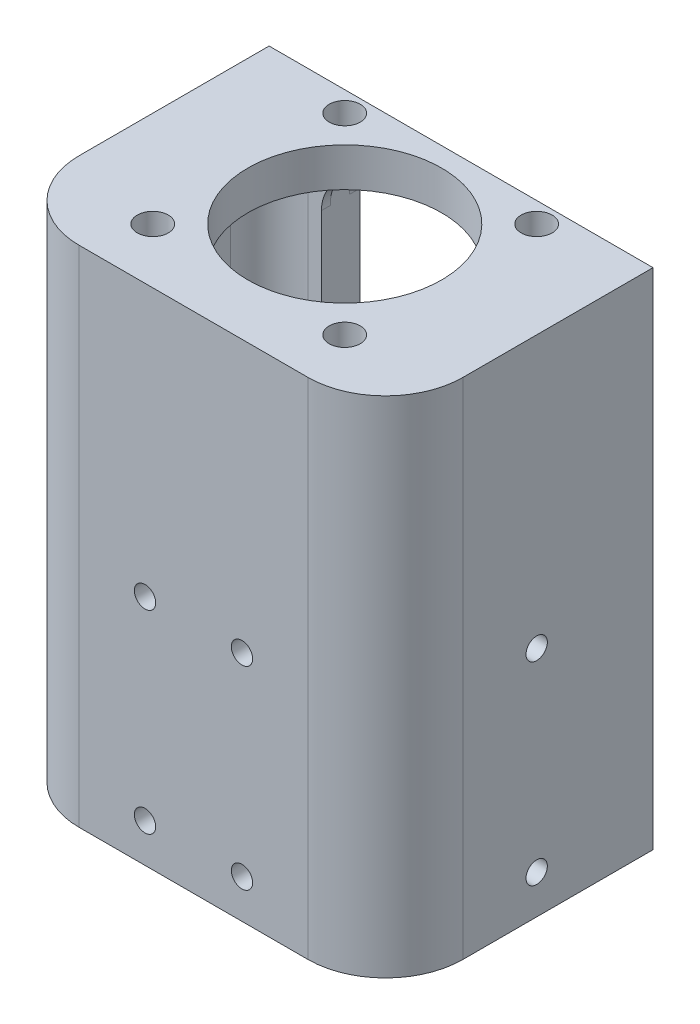
SolidWorks part; units mm, degrees
ref_plane "Front Plane" through (0, 0, 0) normal (0, 0, 1) x (1, 0, 0)
ref_plane "Top Plane" through (0, 0, 0) normal (0, 1, 0) x (1, 0, 0)
ref_plane "Right Plane" through (0, 0, 0) normal (1, 0, 0) x (0, 0, -1)
sketch "Sketch2" plane through (0, 0, 0) normal (0, 1, 0) x (1, 0, 0)
  line L1 (-39.5, -29) -> (39.5, -29) construction
  line L2 (-39.5, -29) -> (-39.5, 29) construction
  line L3 (-39.5, 29) -> (39.5, 29) construction
  line L4 (39.5, -29) -> (39.5, 29) construction
  line L5 (-39.5, -29) -> (39.5, 29) construction
  line L6 (-39.5, 29) -> (39.5, -29) construction
  line L7 (-49.5, 30) -> (49.5, 30)
  line L8 (-49.5, 30) -> (-49.5, -39)
  line L9 (-49.5, -39) -> (49.5, -39)
  line L10 (49.5, 30) -> (49.5, -39)
  circle A0 centre (0, 0) radius 25
  point P0 (0, 0)
  point P10 (0, 30)
  dimension "D5" = 50
  dimension "D1" = 58
  dimension "D2" = 79
  dimension "D3" = 10
  dimension "D4" = 10
  dimension "D6" = 30
extrude "Boss-Extrude1" add sketch "Sketch2" along normal blind 10
sketch "Sketch3" plane through (0, 0, 0) normal (0, -1, 0) x (1, 0, 0)
  line L0 (-49.5, -30) -> (-49.5, 39)
  line L1 (-49.5, 39) -> (49.5, 39)
  line L2 (49.5, 39) -> (49.5, -30)
  line L3 (49.5, -30) -> (39.5, -30)
  line L4 (-49.5, -30) -> (49.5, -30) construction
  line L5 (39.5, -30) -> (39.5, 29)
  line L6 (39.5, 29) -> (-39.5, 29)
  line L7 (-39.5, 29) -> (-39.5, -30)
  line L8 (-39.5, -30) -> (-49.5, -30)
  line L9 (39.5, 29) -> (39.5, -29) construction
extrude "Boss-Extrude2" add sketch "Sketch3" along normal blind 120
hole_wizard "CBORE for M5 SHCS1" positions "Sketch4" profile "Sketch5" counterbore size "M5" standard "ANSI Metric" end condition through all
sketch "Sketch4" plane through (0, 10, 0) normal (0, 1, 0) x (1, 0, 0)
  line L1 (-24.7487, 24.7487) -> (24.7487, 24.7487)
  line L2 (-24.7487, 24.7487) -> (-24.7487, -24.7487)
  line L3 (-24.7487, -24.7487) -> (24.7487, -24.7487)
  line L4 (24.7487, 24.7487) -> (24.7487, -24.7487)
  circle A0 centre (0, 0) radius 35
  point P5 (-24.7487, 24.7487)
  point P6 (24.7487, -24.7487)
  point P91 (-24.7487, -24.7487)
  point P92 (24.7487, 24.7487)
  dimension "D1" = 70
sketch "Sketch5" plane through (24.7487, 10, -24.7487) normal (1, 0, 0) x (0, 0, 1)
  line L0 (0, 0) -> (0, 130)
  line L1 (0, 130) -> (2.75, 130)
  line L3 (2.75, 130) -> (2.75, 7)
  line L4 (2.75, 7) -> (4, 7)
  line L5 (4, 7) -> (4, 0)
  line L7 (4, 0) -> (0, 0)
  line L11 (0, -6.35) -> (0, 107.95) construction
  dimension "Thru Hole Dia." = 5.5
  dimension "Thru Hole Depth" = 130
  dimension "C'Bore Dia." = 8
  dimension "C'Bore Depth" = 7
hole_wizard "M5 Clearance Hole1" positions "Sketch6" profile "Sketch8" hole size "M5" standard "ANSI Metric" end condition through all
sketch "Sketch6" plane through (0, 0, 39) normal (0, 0, 1) x (1, 0, 0)
  line L1 (-12.5, -60) -> (12.5, -60)
  line L2 (-12.5, -60) -> (-12.5, -110)
  line L3 (-12.5, -110) -> (12.5, -110)
  line L4 (12.5, -60) -> (12.5, -110)
  point P9 (-12.5, -60)
  point P10 (12.5, -110)
  point P79 (-12.5, -110)
  point P80 (12.5, -60)
  point P92 (0, -60)
  dimension "D1" = 25
  dimension "D2" = 60
  dimension "D3" = 50
sketch "Sketch8" plane through (-12.5, -60, 39) normal (1, 0, 0) x (0, -1, 0)
  line L0 (0, 0) -> (0, 69)
  line L1 (0, 69) -> (2.75, 69)
  line L2 (2.75, 69) -> (2.75, 0)
  line L5 (2.75, 0) -> (0, 0)
  line L11 (0, -6.35) -> (0, 107.95) construction
  dimension "Thru Hole Dia." = 5.5
  dimension "Thru Hole Depth" = 69
hole_wizard "M5 Clearance Hole2" positions "Sketch9" profile "Sketch10" hole size "M5" standard "ANSI Metric" end condition up to next
sketch "Sketch9" plane through (49.5, 0, 0) normal (1, 0, 0) x (0, 0, -1)
  line L0 (-39, -107.25) -> (-39, -112.75) construction
  line L1 (-39, -57.25) -> (-39, -62.75) construction
  line L2 (-39, -107.25) -> (-39, -112.75)
  line L3 (-39, -57.25) -> (-39, -62.75)
  point P0 (0, -60)
  point P2 (0, -110)
  point P10 (-39, -60)
  point P12 (-39, -110)
sketch "Sketch10" plane through (49.5, -60, 0) normal (0, 1, 0) x (0, 0, -1)
  line L0 (0, 0) -> (0, 10)
  line L1 (0, 10) -> (2.75, 10)
  line L2 (2.75, 10) -> (2.75, 0)
  line L5 (2.75, 0) -> (0, 0)
  line L11 (0, -6.35) -> (0, 107.95) construction
  dimension "Thru Hole Dia." = 5.5
  dimension "Thru Hole Depth" = 10
sketch "Sketch11" plane through (-39.5, 0, 0) normal (1, 0, 0) x (0, 0, -1)
  line L0 (30, 0) -> (-29, 0) construction
  line L1 (20, 0) -> (30, 0)
  line L2 (20, 0) -> (20, -120)
  line L3 (20, -120) -> (30, -120)
  line L4 (30, 0) -> (30, -120)
  dimension "D1" = 10
extrude "Boss-Extrude3" add sketch "Sketch11" along normal blind 13.5
fillet "Fillet1" radius 20 2 edges at (-49.5, -55, 39) (49.5, -55, 39)
fillet "Fillet2" radius 10 6 edges at (39.5, 0, -0.5) (-39.5, 0, 4.5) (-39.5, -60, 29) (39.5, -60, 29) (-26, 0, -28.5988) (-39.5, -60, -20)
